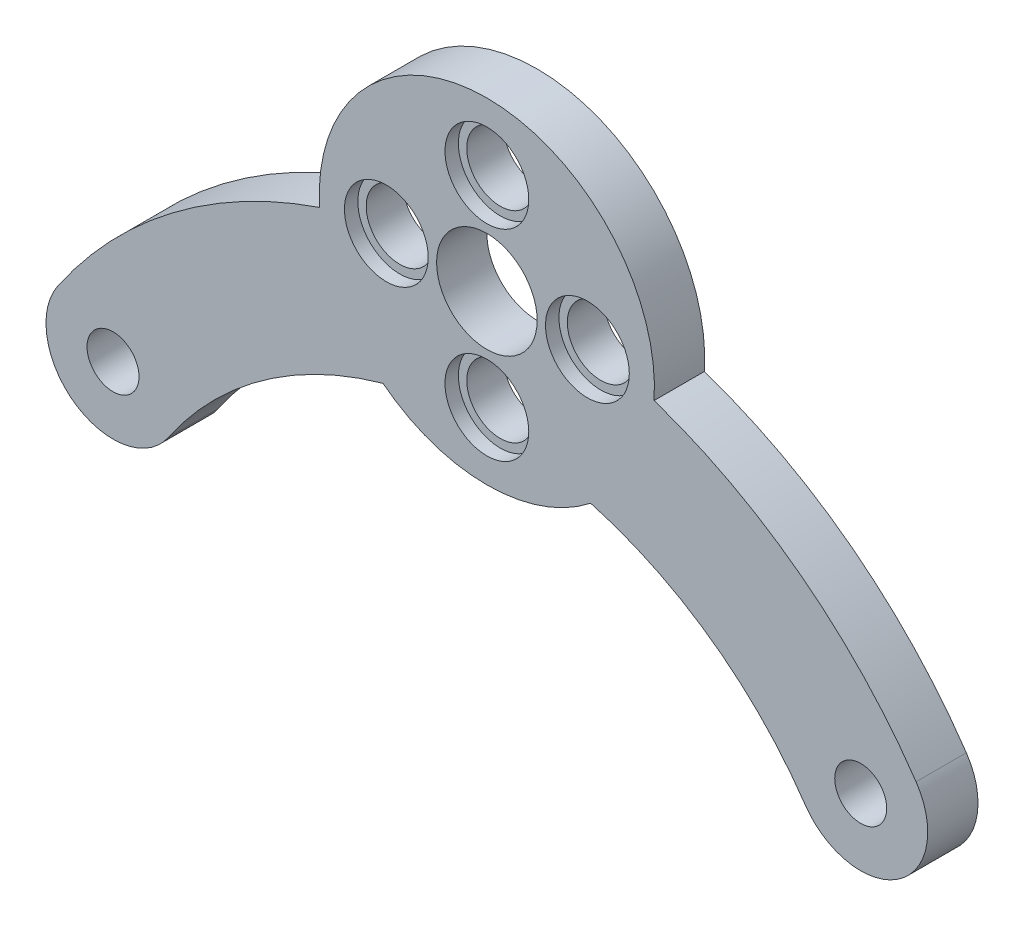
SolidWorks part; units mm, degrees
ref_plane "Front" through (0, 0, 0) normal (0, 0, 1) x (1, 0, 0)
ref_plane "Top" through (0, 0, 0) normal (0, 1, 0) x (1, 0, 0)
ref_plane "Right" through (0, 0, 0) normal (1, 0, 0) x (0, 0, -1)
sketch "Esquisse1" plane through (0, 0, 0) normal (0, 0, 1) x (1, 0, 0)
  line L0 (0, 0) -> (0, 30) construction
  line L1 (0, 30) -> (0, 40) construction
  line L2 (27.9166, 13.4783) -> (20.7123, 10)
  line L3 (20.7123, 10) -> (0, 0) construction
  line L4 (-27.9166, 13.4783) -> (-20.7123, 10)
  arc A0 (9.9789, 29.35) -> (-9.9789, 29.35) centre (0, 30) ccw
  arc A1 (-20.7123, 10) -> (20.7123, 10) centre (0, 0) cw
  arc A2 (9.9789, 29.35) -> (27.9166, 13.4783) centre (0, 0) cw
  arc A3 (-9.9789, 29.35) -> (-27.9166, 13.4783) centre (0, 0) ccw
  dimension "D2" = 23
  dimension "D1" = 10
  dimension "D3" = 30
  dimension "D4" = 8
  dimension "D5" = 10
extrude "Boss.-Extru.1" add sketch "Esquisse1" along normal blind 3
sketch "Esquisse3" plane through (0, 0, 3) normal (0, 0, 1) x (1, 0, 0)
  circle A0 centre (0, 30) radius 10
  arc A1 (9.9789, 29.35) -> (-9.9789, 29.35) centre (0, 30) ccw construction
extrude "Boss.-Extru.2" add sketch "Esquisse3" against normal up to vertex (3 mm away) up to point (27.9166, 13.4783, 0)
fillet "Congé1" radius 4 4 edges at (-27.9166, 13.4783, 1.5) (-20.7123, 10, 1.5) (20.7123, 10, 1.5) (27.9166, 13.4783, 1.5)
sketch "Esquisse2" plane through (0, 0, 3) normal (0, 0, 1) x (1, 0, 0)
  line L0 (0, 30) -> (6, 30) construction
  circle A0 centre (0, 30) radius 3
  circle A1 centre (6, 30) radius 2
  circle A2 centre (0, 24) radius 2
  circle A3 centre (-6, 30) radius 2
  circle A4 centre (0, 36) radius 2
  point P14 (0, 30)
  dimension "D1" = 6
  dimension "D2" = 4
  dimension "D3" = 6
  dimension "D4" = 4
extrude "Enlèv. mat.-Extru.1" cut sketch "Esquisse2" against normal through all both and the other way through all
sketch "Esquisse4" plane through (0, 0, 3) normal (0, 0, 1) x (1, 0, 0)
  circle A0 centre (22.307, 15.2117) radius 1.55
  circle A1 centre (-22.307, 15.2117) radius 1.55
  dimension "D1" = 3.1
extrude "Enlèv. mat.-Extru.2" cut sketch "Esquisse4" against normal through all both and the other way through all
sketch "Esquisse5" plane through (0, 0, 3) normal (0, 0, 1) x (1, 0, 0)
  circle A0 centre (0, 24) radius 2.5
  circle A1 centre (6, 30) radius 2.5
  circle A2 centre (0, 36) radius 2.5
  circle A3 centre (-6, 30) radius 2.5
  dimension "D1" = 5
extrude "Enlèv. mat.-Extru.3" cut sketch "Esquisse5" against normal blind 0.8
